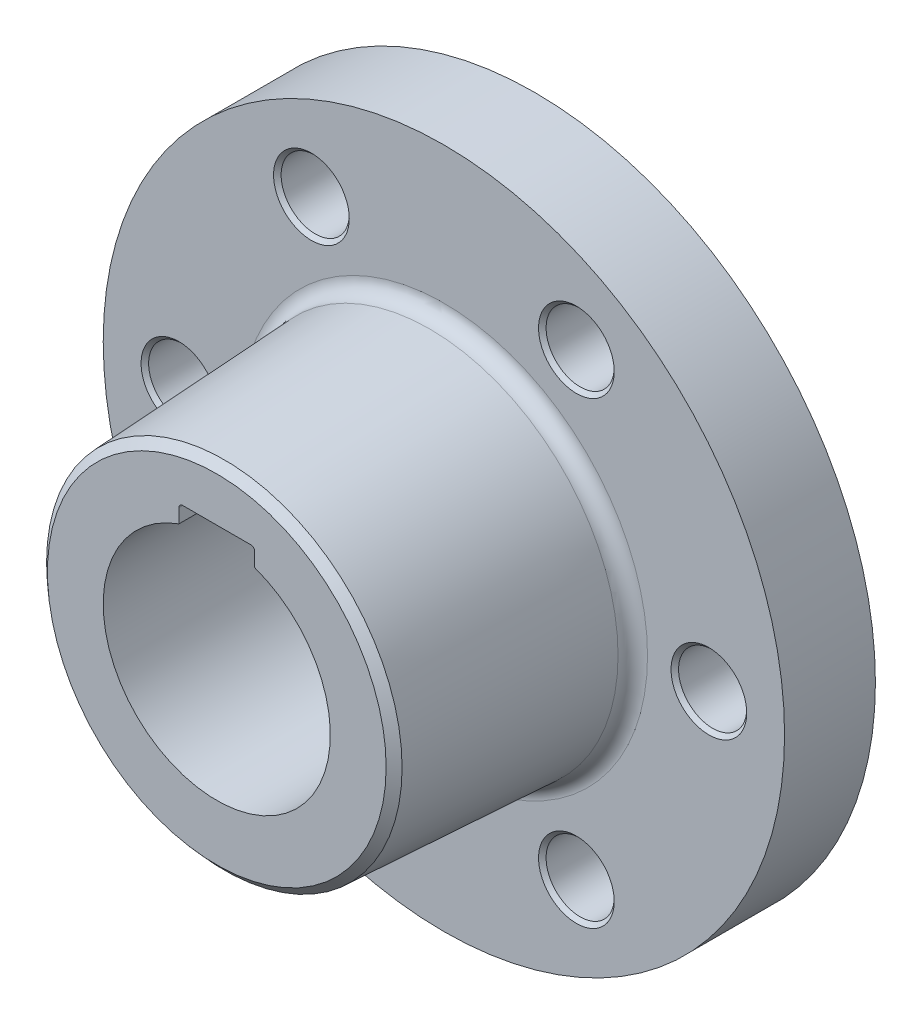
SolidWorks part; units mm, degrees
ref_plane "Přední rovina" through (0, 0, 0) normal (0, 0, 1) x (1, 0, 0)
ref_plane "Vrchní rovina" through (0, 0, 0) normal (0, 1, 0) x (1, 0, 0)
ref_plane "Pravá rovina" through (0, 0, 0) normal (1, 0, 0) x (0, 0, -1)
sketch "Skica1" plane through (0, 0, 0) normal (0, 0, 1) x (1, 0, 0)
  circle A0 centre (0, 0) radius 45
  dimension "D1" = 90
extrude "Přidat vysunutím1" add sketch "Skica1" along normal blind 12
sketch "Skica2" plane through (0, 0, 12) normal (0, 0, 1) x (1, 0, 0)
  circle A0 centre (0, 0) radius 25
  dimension "D1" = 50
extrude "Přidat vysunutím2" add sketch "Skica2" along normal blind 30 draft 3
sketch "Skica3" plane through (0, 0, 42) normal (0, 0, 1) x (1, 0, 0)
  circle A0 centre (0, 0) radius 15
  dimension "D1" = 30
extrude "Odebrat vysunutím1" cut sketch "Skica3" against normal up to next
sketch "Skica4" plane through (0, 0, 42) normal (0, 0, 1) x (1, 0, 0)
  line L0 (0, 26.9275) -> (0, -29.8596) construction
  line L1 (-5, 16.5) -> (5, 16.5)
  line L2 (5, 16.5) -> (5, 13.129)
  line L3 (5, 13.129) -> (-5, 13.129)
  line L4 (-5, 13.129) -> (-5, 16.5)
  point P5 (0, 16.5)
  dimension "D1" = 10
  dimension "D2" = 16.5
extrude "Odebrat vysunutím2" cut sketch "Skica4" against normal up to next
fillet "Zaoblit1" radius 2 1 edges at (25, 0, 12)
sketch "Skica5" plane through (0, 0, 12) normal (0, 0, 1) x (1, 0, 0)
  circle A0 centre (35, 0) radius 4.5
  circle A1 centre (0, 0) radius 35 construction
  dimension "D1" = 9
  dimension "D2" = 70
extrude "Odebrat vysunutím3" cut sketch "Skica5" against normal up to next
chamfer "Zkosení1" distance 0.5 angle 45 1 edges at (39.5, 0, 12)
pattern_circular "Kruhové pole1" count 6 over 360 about axis through (0, 0, 42) along (0, 0, 1) of "Zkosení1", "Odebrat vysunutím3"
fillet "Zaoblit2" radius 0.5 2 edges at (5, 16.5, 21) (-5, 16.5, 21)
chamfer "Zkosení2" distance 1 angle 45 1 edges at (23.4278, 0, 42) first distance on face at (24.9007, 0, 13.8953)
